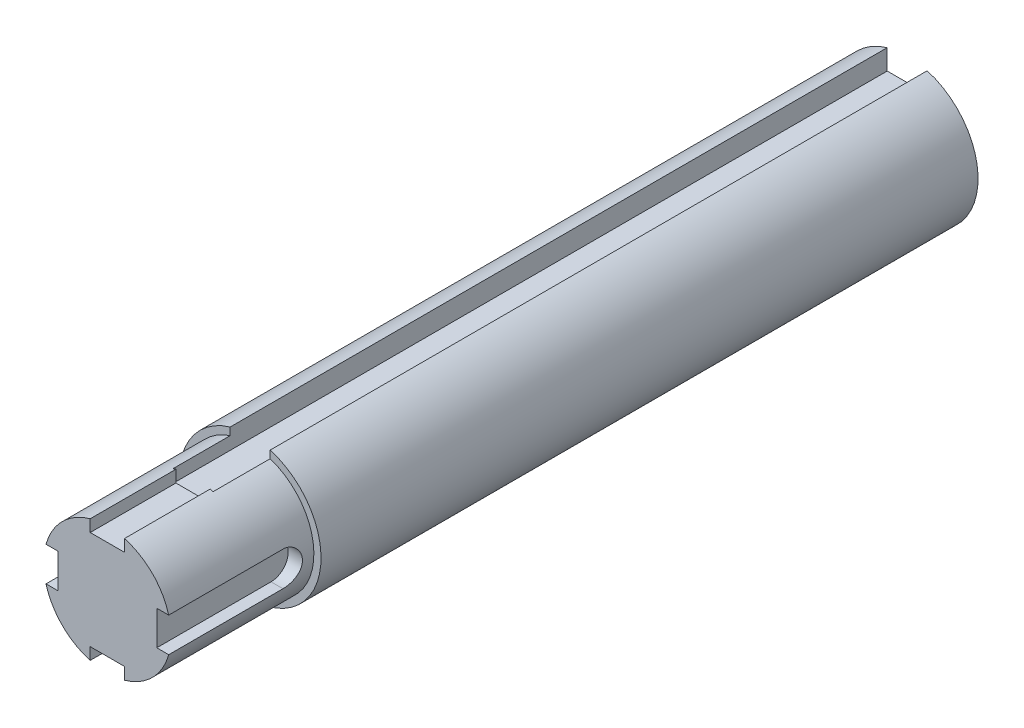
SolidWorks part; units mm, degrees
material "CK45"
ref_plane "Front Plane" through (0, 0, 0) normal (0, 0, 1) x (1, 0, 0)
ref_plane "Top Plane" through (0, 0, 0) normal (0, 1, 0) x (1, 0, 0)
ref_plane "Right Plane" through (0, 0, 0) normal (1, 0, 0) x (0, 0, -1)
sketch "Sketch1" plane through (0, 0, 0) normal (0, 0, 1) x (1, 0, 0)
  circle A0 centre (0, 0) radius 24.8
  dimension "D1" = 49.6
extrude "Boss-Extrude1" add sketch "Sketch1" along normal blind 280
ref_plane "Plane1" through (0, 0, 1) normal (0, 0, -1) x (-1, 0, 0)
sketch "Sketch2" plane through (0, 0, 0) normal (0, 0, -1) x (-1, 0, 0)
  line L1 (-7, 16.7) -> (7, 16.7)
  line L2 (-7, 16.7) -> (-7, 28.1178)
  line L3 (-7, 28.1178) -> (7, 28.1178)
  line L4 (7, 16.7) -> (7, 28.1178)
  line L5 (-7, 16.7) -> (7, 28.1178) construction
  line L6 (-7, 28.1178) -> (7, 16.7) construction
  point P0 (0, 22.4089)
  dimension "D1" = 16.7
  dimension "D2" = 14
extrude "Cut-Extrude1" cut sketch "Sketch2" against normal blind 250
sketch "Sketch3" plane through (0, 0, 0) normal (0, 0, -1) x (-1, 0, 0)
  circle A0 centre (0, 0) radius 7
  dimension "D1" = 14
extrude "Cut-Extrude2" cut sketch "Sketch3" against normal blind 30
thread "Thread1" pitch 1.75 method extrude profile "Thread Profile1" start angle 0, offset 0, length 30, pitch 1.75, diameter 14
ref_plane "Plane2" through (7, 0, 0) normal (0, -1, 0) x (1, 0, 0)
sketch "Thread Profile1" plane through (7, 0, 0) normal (0, -1, 0) x (1, 0, 0)
  line L0 (0, 0) -> (0, 1.75) construction
  line L11 (0, 0) -> (0, 1.5312)
  line L12 (0, 1.5312) -> (-0.9472, 0.9844)
  line L13 (-0.9472, 0.9844) -> (-0.9472, 0.5469)
  line L15 (-0.9472, 0.5469) -> (0, 0)
  line L17 (-0.9472, 0.7656) -> (0, 0.7656) construction
  point P2 (0, 0)
  dimension "Pitch" = 1.75
  dimension "Profile_Angle" = 60
  dimension "Profile_Land" = 0.4375
  dimension "Profile_Height" = 0.9472
sketch "Sketch4" plane through (0, 0, 280) normal (0, 0, 1) x (1, 0, 0)
  circle A0 centre (0, 0) radius 22.3
  dimension "D1" = 44.6
extrude "Cut-Extrude3" cut sketch "Sketch4" against normal blind 50 flip side to cut
ref_plane "Plane3" through (0, -22.3, 0) normal (0, -1, 0) x (0, 0, 1)
sketch "Sketch5" plane through (0, -22.3, 0) normal (0, -1, 0) x (0, 0, 1)
  line L0 (280, 0) -> (240, 0) construction
  line L1 (280, -6) -> (240, -6)
  line L2 (280, 6) -> (240, 6)
  line L3 (280, -22.3) -> (280, 22.3) construction
  arc A0 (280, -6) -> (280, 6) centre (280, 0) ccw
  arc A1 (240, 6) -> (240, -6) centre (240, 0) ccw
  point P2 (260, 0)
  dimension "D1" = 40
  dimension "D2" = 12
extrude "Cut-Extrude4" cut sketch "Sketch5" against normal blind 5
pattern_circular "CirPattern1" count 4 over 360 about axis through (0, 0, 230) along (0, 0, 1) of "Cut-Extrude4"
